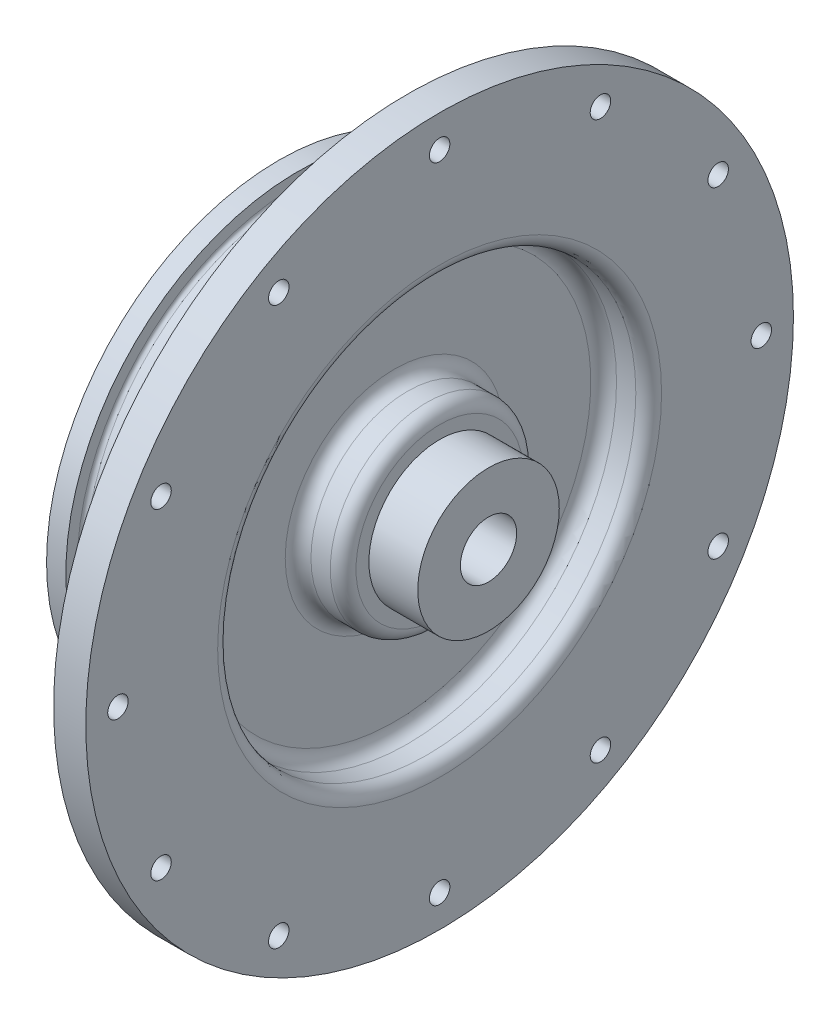
SolidWorks part; units mm, degrees
material "7075-T6 (SN)"
ref_plane "Front Plane" through (0, 0, 0) normal (0, 0, 1) x (1, 0, 0)
ref_plane "Top Plane" through (0, 0, 0) normal (0, 1, 0) x (1, 0, 0)
ref_plane "Right Plane" through (0, 0, 0) normal (1, 0, 0) x (0, 0, -1)
sketch "Sketch1" plane through (0, 0, 0) normal (1, 0, 0) x (0, 0, -1)
  circle A0 centre (0, 0) radius 69.85
  dimension "D1" = 139.7
extrude "Boss-Extrude1" add sketch "Sketch1" along normal blind 6.35
sketch "Sketch2" plane through (0, 0, 0) normal (-1, 0, 0) x (0, 0, 1)
  circle A0 centre (0, 0) radius 45.847
  dimension "D1" = 91.694
extrude "Boss-Extrude2" add sketch "Sketch2" along normal blind 25.4
sketch "Sketch10" plane through (0, 0, 0) normal (0, 1, 0) x (1, 0, 0)
  line L0 (0, 0) -> (-53.2238, 0) construction
  line L1 (-26.2636, 0) -> (26.2636, 0) construction
  line L2 (0, 0) -> (0, 64.5447) construction
  line L3 (0, -62.865) -> (0, 62.865) construction
ref_plane "Plane1" through (0, 0, -45.847) normal (0, 0, -1) x (-1, 0, 0)
sketch "Sketch11" plane through (0, 0, -45.847) normal (0, 0, -1) x (-1, 0, 0)
  line L0 (0, 0) -> (53.2238, 0) construction
  line L1 (0, -45.847) -> (0, 45.847) construction
  circle A0 centre (7.62, 0) radius 1.8986
  dimension "D2" = 3.7973
  dimension "D1" = 7.62
extrude "Cut-Extrude3" cut sketch "Sketch11" against normal blind 10.16
pattern_circular "CirPattern1" count 10 every 36 about axis through (0, 0, 0) along (-1, 0, 0) of "Cut-Extrude3" reverse direction yes
sketch "Sketch15" plane through (6.35, 0, 0) normal (1, 0, 0) x (0, 0, -1)
  circle A0 centre (0, 0) radius 5.5562
  dimension "D1" = 11.1125
extrude "Cut-Extrude4" cut sketch "Sketch15" against normal through all both and the other way through all
sketch "Sketch16" plane through (0, 0, 0) normal (0, 0, 1) x (1, 0, 0)
  line L0 (0, 45.847) -> (-25.4, 45.847) construction
  line L1 (-21.59, 45.847) -> (-14.4018, 45.847)
  line L2 (-21.59, 45.847) -> (-21.59, 43.6245)
  line L3 (-20.828, 42.8625) -> (-15.1638, 42.8625)
  line L4 (-14.4018, 45.847) -> (-14.4018, 43.6245)
  line L5 (0, 0) -> (-53.2238, 0) construction
  line L6 (-25.4, 45.847) -> (-25.4, -45.847) construction
  arc A0 (-14.4018, 43.6245) -> (-15.1638, 42.8625) centre (-15.1638, 43.6245) cw
  arc A1 (-20.828, 42.8625) -> (-21.59, 43.6245) centre (-20.828, 43.6245) cw
  point P8 (-26.6119, 0)
  point P13 (-14.4018, 42.8625)
  point P16 (-21.59, 42.8625)
  dimension "D4" = 0.762
  dimension "D1" = 42.8625
  dimension "D2" = 3.81
  dimension "D3" = 7.1882
revolve "Cut-Revolve1" cut sketch "Sketch16" angle 360 about L0
sketch "Sketch17" plane through (6.35, 0, 0) normal (1, 0, 0) x (0, 0, -1)
  circle A0 centre (0, 0) radius 13.97
  circle A1 centre (0, 0) radius 5.5562
  dimension "D1" = 27.94
  dimension "D2" = 11.1125
extrude "Boss-Extrude3" add sketch "Sketch17" along normal blind 9.652
cosmetic thread "Cosmetic Thread1" parameters "D2"=23.1953
sketch "Sketch18" plane through (0, 0, 0) normal (0, 0, 1) x (1, 0, 0)
  line L0 (6.35, -69.85) -> (6.35, 69.85) construction
  line L1 (6.35, 41.275) -> (-2.54, 41.275)
  line L2 (6.35, 41.275) -> (6.35, 19.05)
  line L3 (6.35, 19.05) -> (-2.54, 19.05)
  line L4 (-2.54, 41.275) -> (-2.54, 19.05)
  line L5 (0, 0) -> (-53.2238, 0) construction
  dimension "D1" = 8.89
  dimension "D2" = 19.05
  dimension "D3" = 41.275
revolve "Cut-Revolve2" cut sketch "Sketch18" angle 360 about L0
fillet "Fillet1" radius 2.54 4 edges at (6.35, 0, -41.275) (-2.54, 0, -41.275) (-2.54, 0, -19.05) (6.35, 0, -19.05)
sketch "Sketch19" plane through (6.35, 0, 0) normal (1, 0, 0) x (0, 0, -1)
  line L0 (0, 0) -> (0, 63.5) construction
  circle A0 centre (0, 0) radius 57.15 construction
  circle A1 centre (0, 0) radius 63.5 construction
  circle A2 centre (0, 63.5) radius 2.0193
  circle A3 centre (31.75, 54.9926) radius 2.0193
  circle A4 centre (54.9926, 31.75) radius 2.0193
  circle A5 centre (63.5, 0) radius 2.0193
  circle A6 centre (54.9926, -31.75) radius 2.0193
  circle A7 centre (31.75, -54.9926) radius 2.0193
  circle A8 centre (0, -63.5) radius 2.0193
  circle A9 centre (-31.75, -54.9926) radius 2.0193
  circle A10 centre (-54.9926, -31.75) radius 2.0193
  circle A11 centre (-63.5, 0) radius 2.0193
  circle A12 centre (-54.9926, 31.75) radius 2.0193
  circle A13 centre (-31.75, 54.9926) radius 2.0193
  point P30 (0, 0)
  dimension "D1" = 114.3
  dimension "D2" = 127
  dimension "D3" = 4.0386
  dimension "D4" = 12
extrude "Cut-Extrude5" cut sketch "Sketch19" against normal through all
